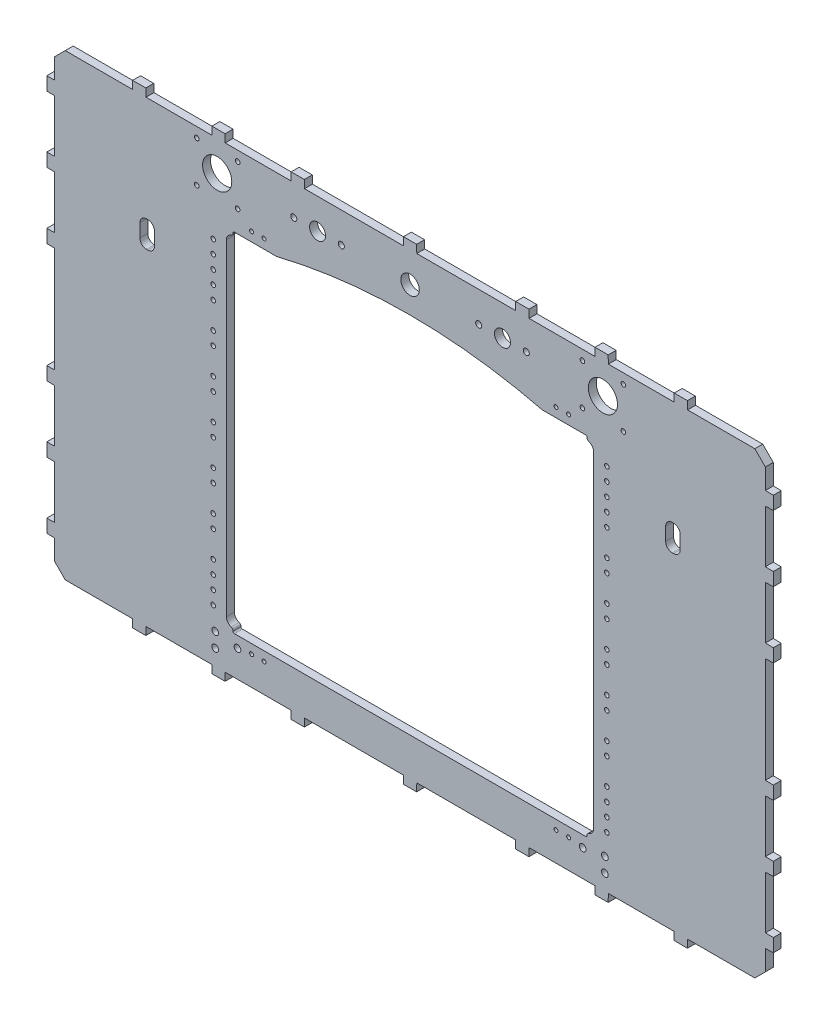
SolidWorks part; units mm, degrees
material "Клен"
ref_plane "Front" through (0, 0, 0) normal (0, 0, 1) x (1, 0, 0)
ref_plane "Top" through (0, 0, 0) normal (0, 1, 0) x (1, 0, 0)
ref_plane "Right" through (0, 0, 0) normal (1, 0, 0) x (0, 0, -1)
sketch "Эскиз1" plane through (0, 0, 0) normal (0, 0, 1) x (1, 0, 0)
  line L0 (2003.9536, 671.6913) -> (1788.4175, 671.6913) construction
  line L1 (1693.5805, 694.1913) -> (1693.5805, 791.8131) construction
  line L2 (1962.5805, 811.45) -> (1962.5805, 379.7662) construction
  line L3 (1554.5805, 451.4706) -> (1554.5805, 698.6913)
  line L4 (1559.5805, 705.6913) -> (1559.5805, 705.3995)
  line L5 (1560.5805, 706.6913) -> (1592.5638, 706.6913)
  line L6 (1862.5805, 811.45) -> (1862.5805, 379.7662) construction
  line L7 (1495.0805, 662.1297) -> (1494.0805, 662.1297)
  line L8 (1892.0805, 682.1297) -> (1893.0805, 682.1297)
  line L9 (1887.0805, 677.1297) -> (1887.0805, 667.1297)
  line L10 (1892.0805, 662.1297) -> (1893.0805, 662.1297)
  line L11 (1898.0805, 677.1297) -> (1898.0805, 667.1297)
  line L12 (1559.5805, 444.7624) -> (1559.5805, 444.4706)
  line L13 (1560.5805, 443.4706) -> (1826.5797, 443.4706)
  line L14 (1827.5797, 444.7624) -> (1827.5797, 444.4706)
  line L15 (1832.5805, 698.6913) -> (1832.5797, 451.4706)
  line L16 (1827.5805, 705.6913) -> (1827.5805, 705.3995)
  line L17 (1826.5805, 706.6913) -> (1793.6805, 706.6913)
  line L18 (1843.6805, 414.6913) -> (1893.4805, 414.6913)
  line L19 (1887.0805, 682.1297) -> (1898.0805, 662.1297) construction
  line L20 (1524.5805, 795.1278) -> (1524.5805, 392.3884) construction
  line L21 (1424.5805, 392.3884) -> (1424.5805, 795.1278) construction
  line L22 (1424.5805, 738.2913) -> (1418.5805, 738.1913)
  line L23 (1418.5805, 498.1913) -> (1418.5805, 488.1913)
  line L24 (1424.5805, 638.2913) -> (1418.5805, 638.1913)
  line L25 (1424.5805, 728.0913) -> (1424.5805, 688.2913)
  line L26 (1418.5805, 548.1913) -> (1418.5805, 538.1913)
  line L27 (1424.5805, 753.6913) -> (1424.5805, 738.2913)
  line L28 (1418.5805, 538.1913) -> (1424.5805, 538.0913)
  line L29 (1418.5805, 438.1913) -> (1424.5805, 438.0913)
  line L30 (1418.5805, 448.1913) -> (1418.5805, 438.1913)
  line L31 (1418.5805, 738.1913) -> (1418.5805, 728.1913)
  line L32 (1418.5805, 638.1913) -> (1418.5805, 628.1913)
  line L33 (1418.5805, 628.1913) -> (1424.5805, 628.0913)
  line L34 (1424.5805, 448.2913) -> (1418.5805, 448.1913)
  line L35 (1424.5805, 498.2913) -> (1418.5805, 498.1913)
  line L36 (1424.5805, 688.2913) -> (1418.5805, 688.1913)
  line L37 (1418.5805, 678.1913) -> (1424.5805, 678.0913)
  line L38 (1418.5805, 488.1913) -> (1424.5805, 488.0913)
  line L39 (1424.5805, 422.6913) -> (1432.5805, 414.6913)
  line L40 (1418.5805, 688.1913) -> (1418.5805, 678.1913)
  line L41 (1424.5805, 628.0913) -> (1424.5805, 548.2913)
  line L42 (1424.5805, 538.0913) -> (1424.5805, 498.2913)
  line L43 (1424.5805, 488.0913) -> (1424.5805, 448.2913)
  line L44 (1424.5805, 438.0913) -> (1424.5805, 422.6913)
  line L45 (1424.5805, 678.0913) -> (1424.5805, 638.2913)
  line L46 (1424.5805, 548.2913) -> (1418.5805, 548.1913)
  line L47 (1432.5805, 761.6913) -> (1424.5805, 753.6913)
  line L48 (1418.5805, 728.1913) -> (1424.5805, 728.0913)
  line L49 (1432.5805, 761.6913) -> (1483.4805, 761.6913)
  line L50 (1432.5805, 414.6913) -> (1483.4805, 414.6913)
  line L51 (1968.5805, 538.1913) -> (1968.5805, 548.1913)
  line L52 (1962.5805, 498.2913) -> (1962.5805, 538.0913)
  line L53 (1968.5805, 728.1913) -> (1968.5805, 738.1913)
  line L54 (1962.5805, 438.0913) -> (1968.5805, 438.1913)
  line L55 (1962.5805, 628.0913) -> (1968.5805, 628.1913)
  line L56 (1968.5805, 548.1913) -> (1962.5805, 548.2913)
  line L57 (1968.5805, 678.1913) -> (1968.5805, 688.1913)
  line L58 (1962.5805, 688.2913) -> (1962.5805, 728.0913)
  line L59 (1962.5805, 448.2913) -> (1962.5805, 488.0913)
  line L60 (1968.5805, 488.1913) -> (1968.5805, 498.1913)
  line L61 (1962.5805, 548.2913) -> (1962.5805, 628.0913)
  line L62 (1962.5805, 738.2913) -> (1962.5805, 753.6913)
  line L63 (1968.5805, 438.1913) -> (1968.5805, 448.1913)
  line L64 (1962.5805, 638.2913) -> (1962.5805, 678.0913)
  line L65 (1962.5805, 422.6913) -> (1962.5805, 438.0913)
  line L66 (1968.5805, 628.1913) -> (1968.5805, 638.1913)
  line L67 (1968.5805, 738.1913) -> (1962.5805, 738.2913)
  line L68 (1962.5805, 488.0913) -> (1968.5805, 488.1913)
  line L69 (1968.5805, 688.1913) -> (1962.5805, 688.2913)
  line L70 (1968.5805, 498.1913) -> (1962.5805, 498.2913)
  line L71 (1962.5805, 728.0913) -> (1968.5805, 728.1913)
  line L72 (1962.5805, 753.6913) -> (1954.5805, 761.6913)
  line L73 (1954.5805, 414.6913) -> (1962.5805, 422.6913)
  line L74 (1968.5805, 448.1913) -> (1962.5805, 448.2913)
  line L75 (1962.5805, 538.0913) -> (1968.5805, 538.1913)
  line L76 (1968.5805, 638.1913) -> (1962.5805, 638.2913)
  line L77 (1962.5805, 678.0913) -> (1968.5805, 678.1913)
  line L78 (1854.5805, 761.6913) -> (1893.4805, 761.6913)
  line L79 (1887.0805, 662.1297) -> (1898.0805, 682.1297) construction
  line L80 (1903.5805, 767.6913) -> (1893.5805, 767.6913)
  line L81 (1903.6805, 761.6913) -> (1903.5805, 767.6913)
  line L82 (1893.5805, 767.6913) -> (1893.4805, 761.6913)
  line L83 (1483.5805, 767.6913) -> (1483.4805, 761.6913)
  line L84 (1493.5805, 767.6913) -> (1483.5805, 767.6913)
  line L85 (1493.6805, 761.6913) -> (1493.5805, 767.6913)
  line L86 (1493.6805, 761.6913) -> (1532.5805, 761.6913)
  line L87 (1903.6805, 761.6913) -> (1954.5805, 761.6913)
  line L88 (1893.4805, 414.6913) -> (1893.5805, 408.6913)
  line L89 (1903.5805, 408.6913) -> (1903.6805, 414.6913)
  line L90 (1893.5805, 408.6913) -> (1903.5805, 408.6913)
  line L91 (1493.5805, 408.6913) -> (1493.6805, 414.6913)
  line L92 (1483.4805, 414.6913) -> (1483.5805, 408.6913)
  line L93 (1483.5805, 408.6913) -> (1493.5805, 408.6913)
  line L94 (1493.6805, 414.6913) -> (1532.5805, 414.6913)
  line L95 (1903.6805, 414.6913) -> (1954.5805, 414.6913)
  line L96 (1892.5805, 811.45) -> (1892.5805, 392.5098) construction
  line L97 (1494.5805, 795.1278) -> (1494.5805, 392.3884) construction
  line L98 (2003.9536, 706.6913) -> (1401.3159, 706.6913) construction
  line L99 (1489.0805, 677.1297) -> (1489.0805, 667.1297)
  line L104 (1495.0805, 682.1297) -> (1494.0805, 682.1297)
  line L105 (1500.0805, 677.1297) -> (1500.0805, 667.1297)
  line L192 (1613.5805, 408.6913) -> (1613.6805, 414.6913)
  line L193 (1613.6805, 414.6913) -> (1688.4805, 414.6913)
  line L194 (1688.4805, 414.6913) -> (1688.5805, 408.6913)
  line L195 (1688.5805, 408.6913) -> (1698.5805, 408.6913)
  line L196 (1698.5805, 408.6913) -> (1698.6805, 414.6913)
  line L197 (1698.6805, 414.6913) -> (1773.4805, 414.6913)
  line L198 (1773.4805, 414.6913) -> (1773.5805, 408.6913)
  line L199 (1773.5805, 408.6913) -> (1783.5805, 408.6913)
  line L200 (1783.5805, 408.6913) -> (1783.6805, 414.6913)
  line L201 (1783.6805, 414.6913) -> (1833.4805, 414.6913)
  line L202 (1833.4805, 414.6913) -> (1833.5805, 408.6913)
  line L203 (1833.5805, 408.6913) -> (1843.5805, 408.6913)
  line L204 (1843.5805, 408.6913) -> (1843.6805, 414.6913)
  line L233 (1854.5805, 761.6913) -> (1843.6805, 761.6913)
  line L234 (1843.6805, 761.6913) -> (1843.5805, 767.6913)
  line L235 (1843.5805, 767.6913) -> (1833.5805, 767.6913)
  line L236 (1833.5805, 767.6913) -> (1833.4805, 761.6913)
  line L237 (1833.4805, 761.6913) -> (1783.6805, 761.6913)
  line L238 (1783.6805, 761.6913) -> (1783.5805, 767.6913)
  line L239 (1783.5805, 767.6913) -> (1773.5805, 767.6913)
  line L240 (1773.5805, 767.6913) -> (1773.4805, 761.6913)
  line L241 (1773.4805, 761.6913) -> (1698.6805, 761.6913)
  line L242 (1698.6805, 761.6913) -> (1698.5805, 767.6913)
  line L243 (1698.5805, 767.6913) -> (1688.5805, 767.6913)
  line L244 (1688.5805, 767.6913) -> (1688.4805, 761.6913)
  line L245 (1688.4805, 761.6913) -> (1613.6805, 761.6913)
  line L246 (1613.6805, 761.6913) -> (1613.5805, 767.6913)
  line L247 (1613.5805, 767.6913) -> (1603.5805, 767.6913)
  line L248 (1603.5805, 767.6913) -> (1603.4805, 761.6913)
  line L249 (1603.4805, 761.6913) -> (1553.6805, 761.6913)
  line L250 (1553.6805, 761.6913) -> (1553.5805, 767.6913)
  line L251 (1553.5805, 767.6913) -> (1543.5805, 767.6913)
  line L252 (1543.5805, 767.6913) -> (1543.4805, 761.6913)
  line L253 (1543.4805, 761.6913) -> (1532.5805, 761.6913)
  line L281 (1532.5805, 414.6913) -> (1543.4805, 414.6913)
  line L282 (1543.4805, 414.6913) -> (1543.5805, 408.6913)
  line L283 (1543.5805, 408.6913) -> (1553.5805, 408.6913)
  line L284 (1553.5805, 408.6913) -> (1553.6805, 414.6913)
  line L285 (1553.6805, 414.6913) -> (1603.4805, 414.6913)
  line L286 (1603.4805, 414.6913) -> (1603.5805, 408.6913)
  line L287 (1603.5805, 408.6913) -> (1613.5805, 408.6913)
  arc A0 (1893.0805, 662.1297) -> (1898.0805, 667.1297) centre (1893.0805, 667.1297) ccw
  arc A1 (1887.0805, 667.1297) -> (1892.0805, 662.1297) centre (1892.0805, 667.1297) ccw
  arc A2 (1893.0805, 682.1297) -> (1898.0805, 677.1297) centre (1893.0805, 677.1297) cw
  arc A3 (1892.0805, 682.1297) -> (1887.0805, 677.1297) centre (1892.0805, 677.1297) ccw
  arc A4 (1494.0805, 662.1297) -> (1489.0805, 667.1297) centre (1494.0805, 667.1297) cw
  arc A5 (1494.0805, 682.1297) -> (1489.0805, 677.1297) centre (1494.0805, 677.1297) ccw
  arc A6 (1500.0805, 667.1297) -> (1495.0805, 662.1297) centre (1495.0805, 667.1297) cw
  arc A7 (1495.0805, 682.1297) -> (1500.0805, 677.1297) centre (1495.0805, 677.1297) cw
  circle A69 centre (1804.0805, 436.4706) radius 1.5
  circle A70 centre (1813.5805, 436.4706) radius 1.5
  circle A71 centre (1824.2277, 434.9809) radius 2.55
  circle A72 centre (1841.0805, 426.6913) radius 2.55
  circle A73 centre (1841.0805, 437.6913) radius 2.55
  circle A74 centre (1842.5805, 454.1913) radius 1.75
  circle A75 centre (1842.5805, 464.1913) radius 1.75
  circle A76 centre (1842.5805, 474.1913) radius 1.75
  circle A77 centre (1842.5805, 484.1913) radius 1.75
  circle A78 centre (1842.5805, 504.1913) radius 1.75
  circle A79 centre (1842.5805, 514.1913) radius 1.75
  circle A80 centre (1842.5805, 534.1913) radius 1.75
  circle A81 centre (1842.5805, 544.1913) radius 1.75
  circle A82 centre (1842.5805, 564.1913) radius 1.75
  circle A83 centre (1842.5805, 574.1913) radius 1.75
  circle A84 centre (1842.5805, 594.1913) radius 1.75
  circle A85 centre (1842.5805, 604.1913) radius 1.75
  circle A86 centre (1842.5805, 624.1913) radius 1.75
  circle A87 centre (1842.5805, 634.1913) radius 1.75
  circle A88 centre (1842.5805, 654.1913) radius 1.75
  circle A89 centre (1842.5805, 664.1913) radius 1.75
  circle A90 centre (1842.5805, 674.1913) radius 1.75
  circle A91 centre (1842.5805, 684.1913) radius 1.75
  circle A92 centre (1842.5805, 694.1913) radius 1.75
  circle A93 centre (1583.0805, 436.4706) radius 1.5
  circle A94 centre (1573.5805, 436.4706) radius 1.5
  circle A95 centre (1562.9305, 434.9809) radius 2.55
  circle A96 centre (1546.0805, 426.6913) radius 2.55
  circle A97 centre (1546.0805, 437.6913) radius 2.55
  circle A98 centre (1544.5805, 454.1913) radius 1.75
  circle A99 centre (1544.5805, 464.1913) radius 1.75
  circle A100 centre (1544.5805, 474.1913) radius 1.75
  circle A101 centre (1544.5805, 484.1913) radius 1.75
  circle A102 centre (1544.5805, 504.1913) radius 1.75
  circle A103 centre (1544.5805, 514.1913) radius 1.75
  circle A104 centre (1544.5805, 534.1913) radius 1.75
  circle A105 centre (1544.5805, 544.1913) radius 1.75
  circle A106 centre (1544.5805, 564.1913) radius 1.75
  circle A107 centre (1544.5805, 574.1913) radius 1.75
  circle A108 centre (1544.5805, 594.1913) radius 1.75
  circle A109 centre (1544.5805, 604.1913) radius 1.75
  circle A110 centre (1544.5805, 624.1913) radius 1.75
  circle A111 centre (1544.5805, 634.1913) radius 1.75
  circle A112 centre (1544.5805, 654.1913) radius 1.75
  circle A113 centre (1544.5805, 664.1913) radius 1.75
  circle A114 centre (1544.5805, 674.1913) radius 1.75
  circle A115 centre (1544.5805, 684.1913) radius 1.75
  circle A116 centre (1544.5805, 694.1913) radius 1.75
  circle A117 centre (1804.0805, 713.6913) radius 1.5
  circle A118 centre (1813.5805, 713.6913) radius 1.5
  circle A119 centre (1824.0805, 723.1913) radius 1.75
  circle A120 centre (1855.0805, 723.1913) radius 1.75
  circle A121 centre (1839.5805, 738.6913) radius 11.05
  circle A122 centre (1855.0805, 754.1913) radius 1.75
  circle A123 centre (1824.0805, 754.1913) radius 1.75
  circle A124 centre (1781.5805, 738.6913) radius 2.3
  circle A125 centre (1763.5805, 738.6913) radius 6.05
  circle A126 centre (1745.5805, 738.6913) radius 2.3
  circle A127 centre (1693.5805, 738.6913) radius 7
  circle A128 centre (1641.5805, 738.6913) radius 2.3
  circle A129 centre (1623.5805, 738.6913) radius 6.05
  circle A130 centre (1605.5805, 738.6913) radius 2.3
  circle A131 centre (1583.0805, 713.6913) radius 1.5
  circle A132 centre (1573.5805, 713.6913) radius 1.5
  circle A133 centre (1563.0805, 723.1913) radius 1.75
  circle A134 centre (1563.0805, 754.1913) radius 1.75
  circle A135 centre (1547.5805, 738.6913) radius 11.05
  circle A136 centre (1532.0805, 723.1913) radius 1.75
  circle A137 centre (1532.0805, 754.1913) radius 1.75
  arc A142 (1793.6805, 706.6913) -> (1592.5638, 706.6913) centre (1693.1221, 296.6279) ccw
  arc A143 (1558.1519, 703.4829) -> (1554.5805, 698.6913) centre (1559.5805, 698.6913) ccw
  arc A144 (1558.1519, 703.4829) -> (1559.5805, 705.3995) centre (1557.5805, 705.3995) ccw
  arc A145 (1560.5805, 706.6913) -> (1559.5805, 705.6913) centre (1560.5805, 705.6913) ccw
  arc A155 (1559.5805, 444.4706) -> (1560.5805, 443.4706) centre (1560.5805, 444.4706) ccw
  arc A156 (1559.5805, 444.7624) -> (1558.1519, 446.6791) centre (1557.5805, 444.7624) ccw
  arc A157 (1554.5805, 451.4706) -> (1558.1519, 446.6791) centre (1559.5805, 451.4706) ccw
  arc A158 (1826.5797, 443.4706) -> (1827.5797, 444.4706) centre (1826.5797, 444.4706) ccw
  arc A159 (1829.0083, 446.6791) -> (1827.5797, 444.7624) centre (1829.5797, 444.7624) ccw
  arc A160 (1829.0083, 446.6791) -> (1832.5797, 451.4706) centre (1827.5797, 451.4706) ccw
  arc A161 (1832.5805, 698.6913) -> (1829.009, 703.4829) centre (1827.5805, 698.6913) ccw
  arc A162 (1827.5805, 705.3995) -> (1829.009, 703.4829) centre (1829.5805, 705.3995) ccw
  arc A163 (1827.5805, 705.6913) -> (1826.5805, 706.6913) centre (1826.5805, 705.6913) ccw
  point P48 (1892.5805, 672.1297)
  point P49 (1892.5805, 672.1297)
  dimension "D7" = 5
  dimension "D2" = 30
  dimension "D3" = 100
  dimension "D1" = 100
  dimension "D4" = 30
  dimension "D5" = 11
  dimension "D6" = 20
  dimension "D8" = 35
extrude "Бобышка-Вытянуть1" add sketch "Эскиз1" along normal blind 6
